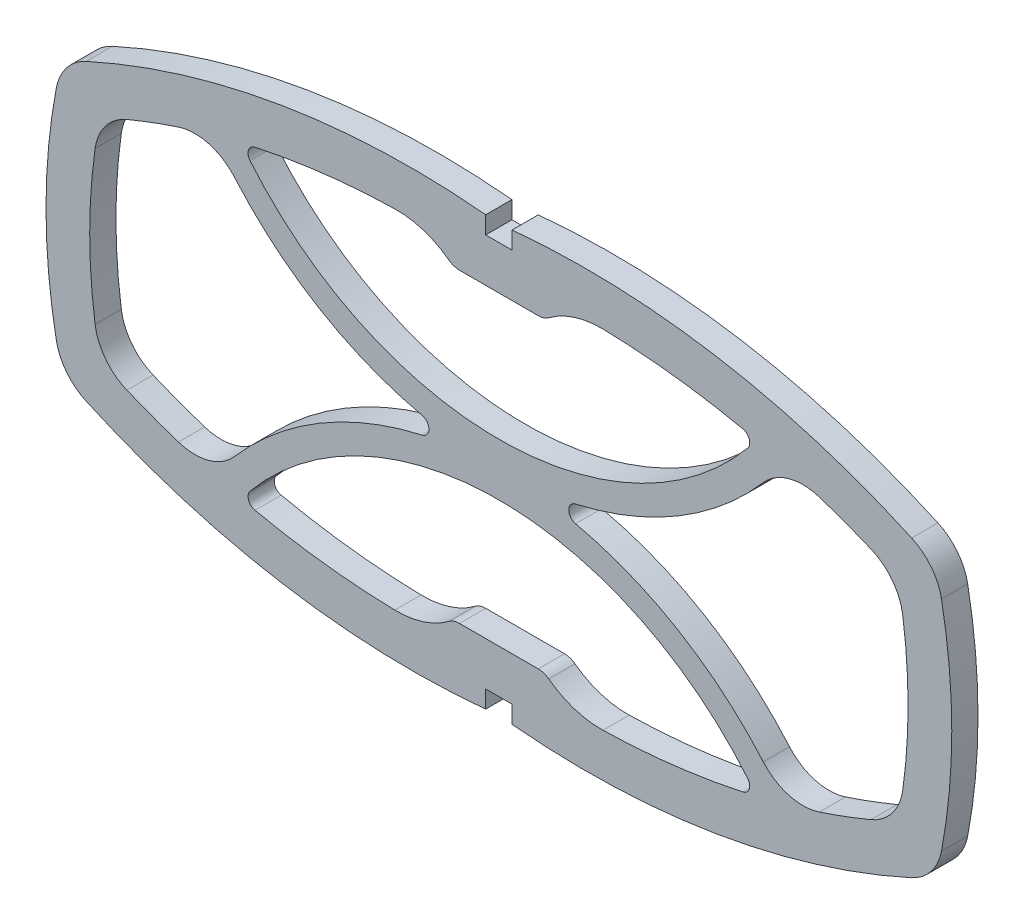
SolidWorks part; units mm, degrees
material "Acrylic (Medium-high impact)"
ref_plane "Front Plane" through (0, 0, 0) normal (0, 0, 1) x (1, 0, 0)
ref_plane "Top Plane" through (0, 0, 0) normal (0, 1, 0) x (1, 0, 0)
ref_plane "Right Plane" through (0, 0, 0) normal (1, 0, 0) x (0, 0, -1)
sketch "Sketch1" plane through (0, 0, 0) normal (0, 0, 1) x (1, 0, 0)
  line L0 (0, 0) -> (0, -50000) construction
  line L1 (0, 0) -> (-50000, 0) construction
  line L2 (0, 0) -> (0, 5)
  line L3 (0, 5) -> (-1.51, 5)
  line L4 (-1.51, 5) -> (-1.51, 7)
  line L5 (0, 0) -> (-1.51, 0)
  line L6 (-1.51, 0) -> (-1.51, -2)
  line L7 (-50, 0) -> (-50, -50000) construction
  line L8 (0, -17.5) -> (-50000, -17.5) construction
  line L9 (-1.51, -35) -> (-1.51, -33)
  line L10 (0, -35) -> (-1.51, -35)
  line L11 (-1.51, -40) -> (-1.51, -42)
  line L12 (0, -40) -> (-1.51, -40)
  line L13 (0, -35) -> (0, -40)
  line L14 (-1.51, -2) -> (-1.51, -33)
  circle A0 centre (-10, -82.5987) radius 90
  circle A1 centre (-10, 47.5987) radius 90
  circle A2 centre (15, -17.5) radius 66.8281
  point P27 (-50, -1.9761)
  dimension "D7" = 180
  dimension "D1" = 1.51
  dimension "D2" = 5
  dimension "D3" = 2
  dimension "D4" = 2
  dimension "D6" = 10
  dimension "D9" = 15
  dimension "D5" = 50
  dimension "D8" = 17.5
extrude "Boss-Extrude1" add sketch "Sketch1" along normal blind 3 contours A0 A2 A1 L11 L12 L13 L10 L9 L14 L6 L5 L2 L3 L4 region at (-24.4537, -17.5, 0)
sketch "Sketch2" plane through (0, 0, 3) normal (0, 0, 1) x (1, 0, 0)
  line L0 (-1.51, 0) -> (-6.51, 0)
  line L1 (-1.51, -35) -> (-6.51, -35)
  line L2 (-1.51, 0) -> (-1.51, -35)
  line L18 (-6.51, -37.3297) -> (-6.51, 2.3297)
  line L19 (-6.51, -37.3297) -> (-6.51, 2.3297)
  arc A6 (-6.51, 2.3297) -> (-45.6386, -5.4307) centre (-10, -82.5987) ccw
  arc A7 (-45.6386, -5.4307) -> (-45.6386, -29.5693) centre (15, -17.5) ccw
  arc A8 (-45.6386, -29.5693) -> (-6.51, -37.3297) centre (-10, 47.5987) ccw
  arc A9 (-6.51, 2.3297) -> (-45.6386, -5.4307) centre (-10, -82.5987) ccw
  arc A10 (-45.6386, -5.4307) -> (-45.6386, -29.5693) centre (15, -17.5) ccw
  arc A11 (-45.6386, -29.5693) -> (-6.51, -37.3297) centre (-10, 47.5987) ccw
  line M12 (-1.51, -35) -> (-1.51, 0)
  dimension "D1" = 5
extrude "Cut-Extrude1" cut sketch "Sketch2" against normal up to next contours A10 A11 L19 A9 | L19 L1 L0 M12 region at (-4.01, -17.5, 3) region at (-24.9462, -17.5, 3)
sketch "Sketch3" plane through (0, 0, 3) normal (0, 0, 1) x (1, 0, 0)
  line L0 (-46.8281, -17.5) -> (49953.1719, -17.5) construction
  line L1 (0, 0) -> (0, -50000) construction
  line L2 (-1.51, -40) -> (-1.51, -42)
  line L3 (0, -40) -> (-1.51, -40)
  line L4 (0, -35) -> (0, -40)
  line L5 (-6.51, -35) -> (0, -35)
  line L6 (-6.51, -37.3297) -> (-6.51, -35)
  line L7 (0, 0) -> (0, -35)
  line L10 (-6.51, 2.3297) -> (-6.51, 0)
  line L11 (-6.51, 0) -> (0, 0)
  line L12 (0, 0) -> (0, 5)
  line L13 (0, 5) -> (-1.51, 5)
  line L14 (-1.51, 5) -> (-1.51, 7)
  line L15 (-1.51, -42) -> (-1.51, -40)
  line L16 (-1.51, -40) -> (0, -40)
  line L17 (0, -40) -> (0, -35)
  line L18 (0, -35) -> (-6.51, -35)
  line L19 (-6.51, -35) -> (-6.51, -37.3297)
  line L20 (-6.51, 2.3297) -> (-6.51, 0)
  line L21 (-6.51, 0) -> (0, 0)
  line L22 (0, 0) -> (0, 5)
  line L23 (0, 5) -> (-1.51, 5)
  line L24 (-1.51, 5) -> (-1.51, 7)
  line L25 (-1.51, -42) -> (-1.51, -40)
  line L26 (-1.51, -40) -> (0, -40)
  line L27 (0, -40) -> (0, -35)
  line L28 (0, -35) -> (-6.51, -35)
  line L29 (-6.51, -35) -> (-6.51, -37.3297)
  circle A0 centre (0, 22.5) radius 40
  arc A1 (-6.51, -37.3297) -> (-45.6386, -29.5693) centre (-10, 47.5987) cw
  circle A2 centre (0, 22.5) radius 37
  arc A3 (-1.51, -42) -> (-50, -33.0239) centre (-10, 47.5987) cw
  circle A4 centre (0, -57.5) radius 37
  circle A5 centre (0, -57.5) radius 40
  arc A6 (-1.51, 7) -> (-50, -1.9761) centre (-10, -82.5987) ccw
  arc A7 (-50, -1.9761) -> (-50, -33.0239) centre (15, -17.5) ccw
  arc A8 (-50, -33.0239) -> (-1.51, -42) centre (-10, 47.5987) ccw
  arc A9 (-45.6386, -29.5693) -> (-6.51, -37.3297) centre (-10, 47.5987) ccw
  arc A10 (-45.6386, -5.4307) -> (-45.6386, -29.5693) centre (15, -17.5) ccw
  arc A11 (-6.51, 2.3297) -> (-45.6386, -5.4307) centre (-10, -82.5987) ccw
  arc A12 (-1.51, 7) -> (-50, -1.9761) centre (-10, -82.5987) ccw
  arc A13 (-50, -1.9761) -> (-50, -33.0239) centre (15, -17.5) ccw
  arc A14 (-50, -33.0239) -> (-1.51, -42) centre (-10, 47.5987) ccw
  arc A15 (-45.6386, -29.5693) -> (-6.51, -37.3297) centre (-10, 47.5987) ccw
  arc A16 (-45.6386, -5.4307) -> (-45.6386, -29.5693) centre (15, -17.5) ccw
  arc A17 (-6.51, 2.3297) -> (-45.6386, -5.4307) centre (-10, -82.5987) ccw
  circle A18 centre (-9, -17.5) radius 1
  point P32 (-46.8281, -17.5)
  arc M32 (-45.6386, -5.4307) -> (-6.51, 2.3297) centre (-10, -82.5987) cw
  dimension "D2" = 80
  dimension "D3" = 3
  dimension "D4" = 2
  dimension "D8" = 40
  dimension "D1" = 0
extrude "Boss-Extrude8" add sketch "Sketch3" against normal up to surface (3 mm away) contours A2 A0 L7 M32 | A18 A5 A0 | A5 A1 A4 L7 region at (-16.7944, -24.3874, 3) region at (-16.7944, -10.6126, 3) region at (-6.1254, -17.5, 3) up to face at (-14.2845, -17.5, 0)
mirror "Mirror1" about plane through (0, 0, 3) normal (-1, 0, 0) of "Boss-Extrude8", "Cut-Extrude1", "Boss-Extrude1"
fillet "Fillet1" radius 2 4 edges at (-6.51, -35, 1.5) (6.51, -35, 1.5) (6.51, 0, 1.5) (-6.51, 0, 1.5)
fillet "Fillet2" radius 10 4 edges at (-6.51, 2.3297, 1.5) (6.51, 2.3297, 1.5) (6.51, -37.3297, 1.5) (-6.51, -37.3297, 1.5)
fillet "Fillet3" radius 6 12 edges at (-45.6386, -5.4307, 1.5) (-50, -1.9761, 1.5) (-50, -33.0239, 1.5) (-45.6386, -29.5693, 1.5) (50, -33.0239, 1.5) (50, -1.9761, 1.5) (45.6386, -29.5693, 1.5) (45.6386, -5.4307, 1.5) (32.612, -34.3385, 1.5) (32.612, -0.6615, 1.5) (-32.612, -0.6615, 1.5) (-32.612, -34.3385, 1.5)
fillet "Fillet4" radius 1 4 edges at (-29.4788, 0.1393, 1.5) (29.4788, 0.1393, 1.5) (29.4788, -35.1393, 1.5) (-29.4788, -35.1393, 1.5)
equation "\"D4@Sketch1\"=\"D3@Sketch1\""
